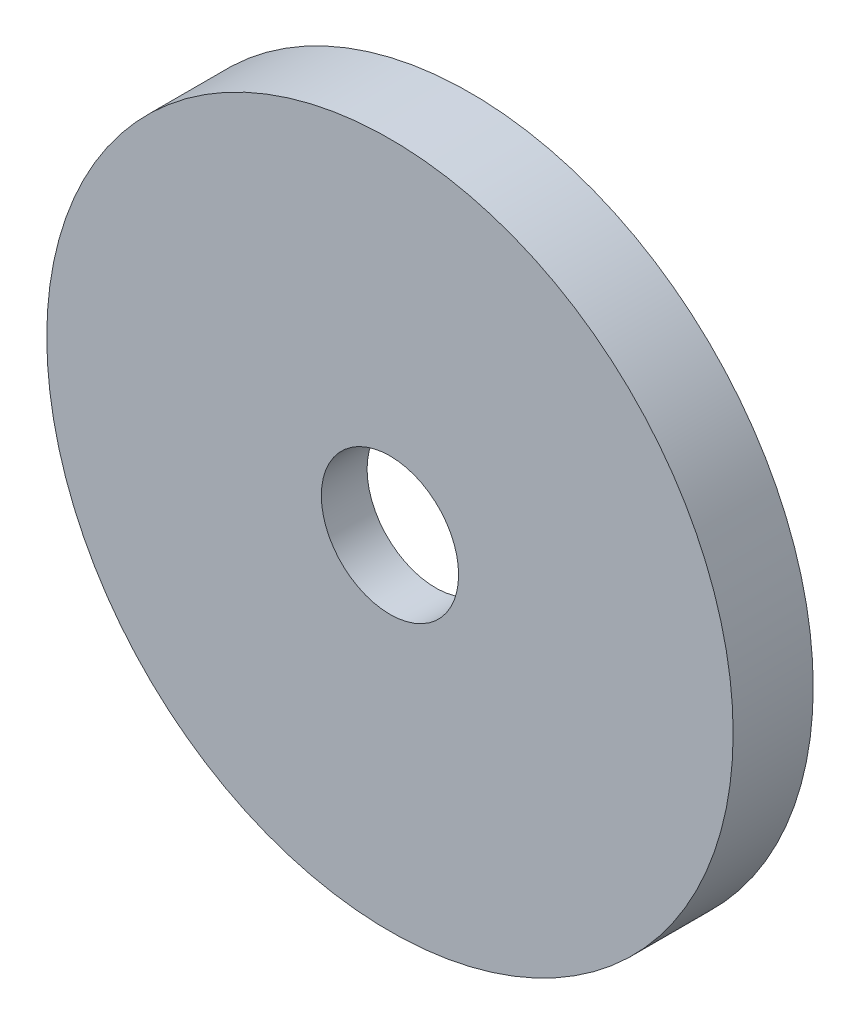
SolidWorks part; units mm, degrees
ref_plane "Front Plane" through (0, 0, 0) normal (0, 0, 1) x (1, 0, 0)
ref_plane "Top Plane" through (0, 0, 0) normal (0, 1, 0) x (1, 0, 0)
ref_plane "Right Plane" through (0, 0, 0) normal (1, 0, 0) x (0, 0, -1)
sketch "Sketch2" plane through (0, 0, 0) normal (0, 0, 1) x (1, 0, 0)
  circle A0 centre (0, 0) radius 30
  dimension "D1" = 60
extrude "Boss-Extrude1" add sketch "Sketch2" along normal blind 6 contours A0
sketch "Sketch3" plane through (0, 0, 0) normal (0, 0, -1) x (-1, 0, 0)
  circle A0 centre (0, 0) radius 8
extrude "Cut-Extrude1" cut sketch "Sketch3" against normal blind 2
sketch "Sketch4" plane through (0, 0, 2) normal (0, 0, -1) x (-1, 0, 0)
  circle A0 centre (0, 0) radius 6
  dimension "D1" = 12
sketch "Sketch5" plane through (0, 0, 0) normal (0, 0, -1) x (-1, 0, 0)
  circle A0 centre (0, 0) radius 8
  circle A1 centre (0, 0) radius 30
extrude "Cut-Extrude3" cut sketch "Sketch5" against normal blind 2
sketch "Sketch7" plane through (0, 0, 2) normal (0, 0, -1) x (-1, 0, 0)
  circle A0 centre (0, 0) radius 30 construction
  circle A1 centre (0, 0) radius 30
  circle A2 centre (0, 0) radius 20
extrude "Boss-Extrude3" add sketch "Sketch7" along normal blind 3
sketch "Sketch9" plane through (0, 0, 0) normal (0, 1, 0) x (1, 0, 0)
  line L0 (23, 4.4385) -> (23, -9.579) construction
  line L1 (30, -6) -> (30, 4.4385) construction
  line L2 (-30, -6) -> (30, -6) construction
  line L4 (25, 16.5) -> (21, 16.5)
  line L5 (25, 16.5) -> (25, -3.5)
  line L6 (25, -3.5) -> (21, -3.5)
  line L7 (21, 16.5) -> (21, -3.5)
  line L8 (27.6, -3.5) -> (18.4, -3.5)
  line L9 (27.6, -3.5) -> (27.6, -4.2352)
  line L10 (27.6, -4.2352) -> (18.4, -4.2352)
  line L11 (18.4, -3.5) -> (18.4, -4.2352)
  dimension "D1" = 7
  dimension "D2" = 4
  dimension "D3" = 9.2
  dimension "D4" = 2.5
  dimension "D5" = 20
sketch "Sketch10" plane through (0, 0, -1) normal (0, 1, 0) x (1, 0, 0)
  line L0 (-30, -7) -> (30, -7) construction
  line L1 (27.8253, -7) -> (21.2987, -7)
  line L2 (27.8253, -7) -> (27.8253, 17.914)
  line L3 (27.8253, 17.914) -> (21.2987, 17.914)
  line L4 (21.2987, -7) -> (21.2987, 17.914)
sketch "Sketch11" plane through (0, 0, -1) normal (0, 1, 0) x (1, 0, 0)
  line L0 (23, 25.9336) -> (23, -31.2164) construction
  line L1 (30, -7) -> (30, -4.13) construction
  line L2 (27.6, -4.7176) -> (18.4, -4.7176)
  line L3 (27.6, -4.7176) -> (27.6, -4.5)
  line L4 (27.6, -4.5) -> (18.4, -4.5)
  line L5 (18.4, -4.7176) -> (18.4, -4.5)
  line L6 (25.5, -4.5) -> (20.5, -4.5)
  line L7 (25.5, -4.5) -> (25.5, 15.5)
  line L8 (25.5, 15.5) -> (20.5, 15.5)
  line L9 (20.5, -4.5) -> (20.5, 15.5)
  line L10 (-30, -7) -> (30, -7) construction
  line L11 (30, -5.565) -> (30, 15.8013) construction
  line L12 (20.026, -1.9778) -> (20.026, 1.2006) construction
  dimension "D1" = 9.2
  dimension "D2" = 20
  dimension "D3" = 5
  dimension "D4" = 7
  dimension "D5" = 2.5
  dimension "D6" = 0.474
extrude "Cut-Extrude4" cut sketch "Sketch4" against normal blind 10 contours A0
